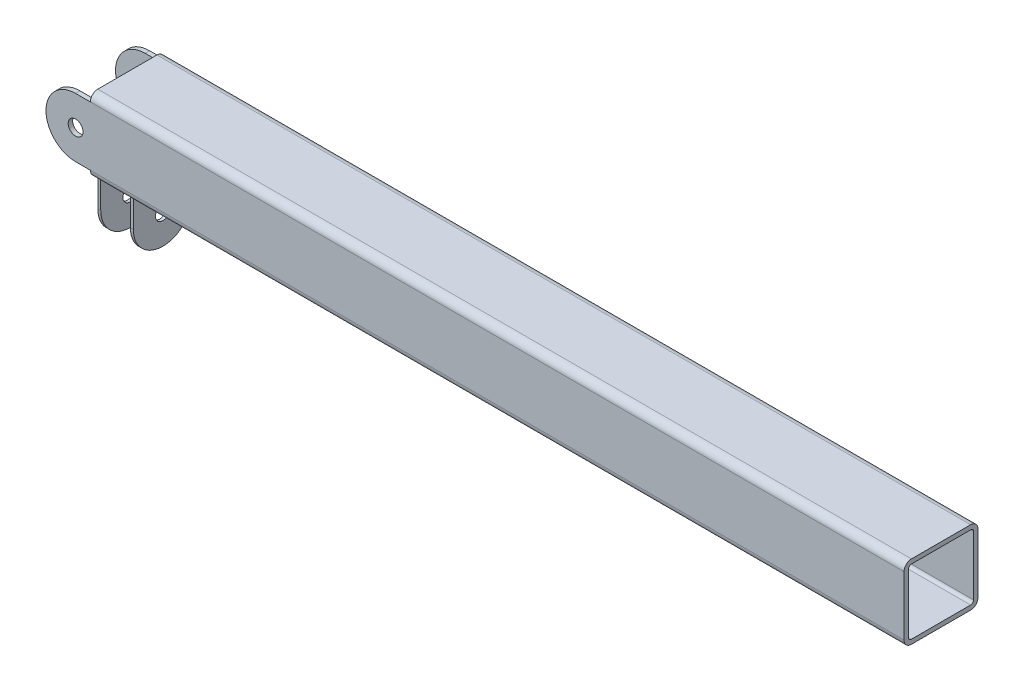
SolidWorks part; units mm, degrees
ref_plane "Front Plane" through (0, 0, 0) normal (0, 0, 1) x (1, 0, 0)
ref_plane "Top Plane" through (0, 0, 0) normal (0, 1, 0) x (1, 0, 0)
ref_plane "Right Plane" through (0, 0, 0) normal (1, 0, 0) x (0, 0, -1)
sketch "Sketch1" plane through (0, 0, 0) normal (1, 0, 0) x (0, 0, -1)
  line L1 (-20, -25) -> (20, -25)
  line L2 (-25, -20) -> (-25, 20)
  line L3 (-20, 25) -> (20, 25)
  line L4 (25, -20) -> (25, 20)
  line L5 (-25, -25) -> (25, 25) construction
  line L6 (-25, 25) -> (25, -25) construction
  arc A0 (-20, -25) -> (-25, -20) centre (-20, -20) cw
  arc A1 (20, -25) -> (25, -20) centre (20, -20) ccw
  arc A2 (20, 25) -> (25, 20) centre (20, 20) cw
  arc A3 (-25, 20) -> (-20, 25) centre (-20, 20) cw
  point P0 (0, 0)
  dimension "D3" = 5
  dimension "D1" = 50
  dimension "D2" = 50
extrude "Extrude-Thin1" add sketch "Sketch1" along normal blind 550 thin thin type one direction reverse wall 3
sketch "Sketch3" plane through (0, 0, -25) normal (0, 0, -1) x (-1, 0, 0)
  line L0 (0, 20) -> (10, 20)
  line L1 (0, -20) -> (10, -20)
  line L2 (0, -20) -> (0, 20) construction
  line L3 (0, -20) -> (0, 20)
  arc A0 (10, 20) -> (10, -20) centre (10, 0) cw
  circle A1 centre (10, 0) radius 5
  dimension "D1" = 10
  dimension "D2" = 10
  dimension "D3" = 20
  dimension "D4" = 10
extrude "Boss-Extrude2" add sketch "Sketch3" against normal up to surface (3 mm away) up to face at (275, 0, -22)
extrude "Boss-Extrude3" add sketch "Sketch3<3>" against normal up to surface (50 mm away) from surface up to face at (275, 0, 25) starting at face at (275, 0, 22)
sketch "Sketch3<3>" plane through (0, 0, -25) normal (0, 0, -1) x (-1, 0, 0) same geometry as "Sketch3"
sketch "Sketch5" plane through (0, -25, 0) normal (0, -1, 0) x (-1, 0, 0)
  line L0 (-22, 20) -> (-22, -20)
  line L1 (-22, 20) -> (-24, 20)
  line L2 (-22, -20) -> (-24, -20)
  line L3 (-24, 20) -> (-24, -20)
  line L5 (-2, 20) -> (-2, -20)
  line L6 (-2, 20) -> (0, 20)
  line L7 (-2, -20) -> (0, -20)
  line L8 (0, 20) -> (0, -20)
  line L9 (0, -20) -> (0, 20) construction
  line L10 (-550, 20) -> (0, 20) construction
  line L12 (-40, 20) -> (-40, -20) construction
  point P4 (0, 0)
  dimension "D1" = 40
  dimension "D2" = 2
  dimension "D3" = 20
extrude "Boss-Extrude4" add sketch "Sketch5" along normal blind 40 separate body
fillet "Fillet1" radius 20 2 edges at (23, -65, -20) (23, -65, 20)
fillet "Fillet2" radius 20 2 edges at (1, -65, -20) (1, -65, 20)
sketch "Sketch6" plane through (0, 0, 0) normal (-1, 0, 0) x (0, 0, 1)
  circle A0 centre (0, -45) radius 5
  arc A1 (-20, -45) -> (0, -65) centre (0, -45) ccw construction
  dimension "D1" = 10
extrude "Cut-Extrude2" cut sketch "Sketch6" against normal through all
